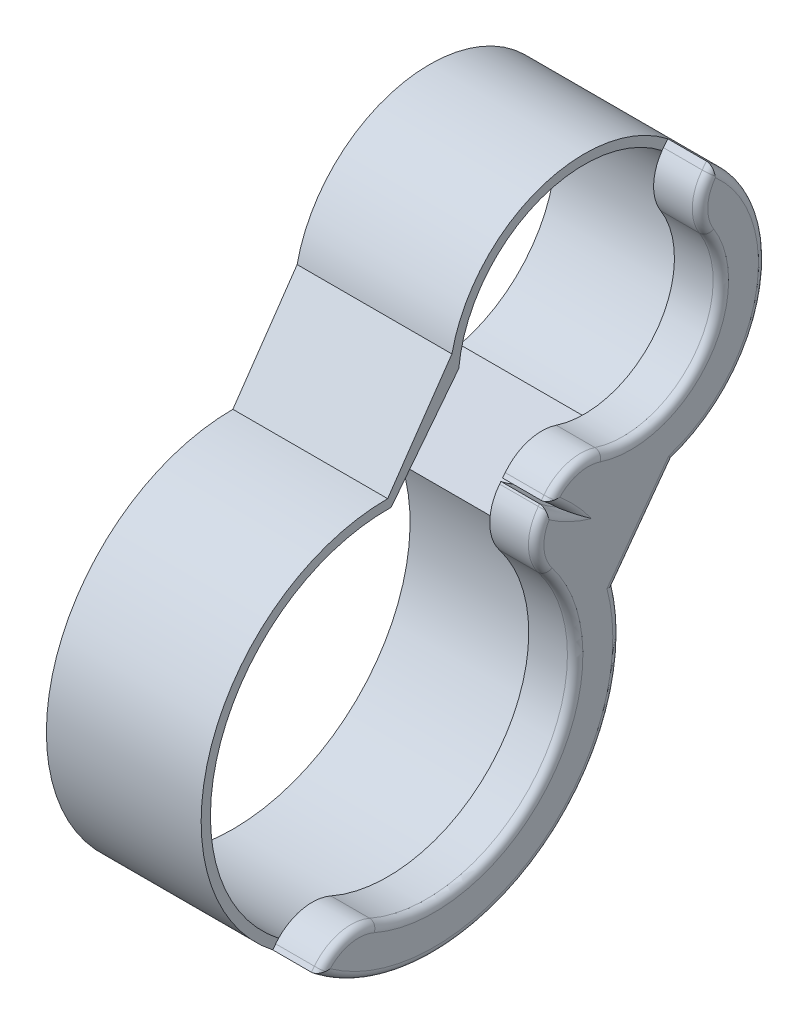
SolidWorks part; units mm, degrees
ref_plane "Front Plane" through (0, 0, 0) normal (0, 0, 1) x (1, 0, 0)
ref_plane "Top Plane" through (0, 0, 0) normal (0, 1, 0) x (1, 0, 0)
ref_plane "Right Plane" through (0, 0, 0) normal (1, 0, 0) x (0, 0, -1)
sketch "Sketch1" plane through (0, 0, 0) normal (1, 0, 0) x (0, 0, -1)
  line L0 (-26.7095, -28.8833) -> (-22.337, -23.2947)
  line L1 (-16.0369, -36.8188) -> (-12.2646, -31.9973)
  line L2 (-11.4506, -32.385) -> (-15.2204, -37.5072)
  line L3 (-22.7828, -22.2598) -> (-26.9349, -28.2811)
  circle A0 centre (-26.9349, -40.3311) radius 3
  circle A1 centre (-14.2256, -24.0867) radius 3
  arc A2 (-12.2646, -31.9973) -> (-22.337, -23.2947) centre (-14.2256, -24.0867) cw construction
  arc A3 (-26.7095, -28.8833) -> (-16.0369, -36.8188) centre (-26.9349, -40.3311) cw
  circle A4 centre (-26.9349, -40.3311) radius 11.45
  circle A5 centre (-14.2256, -24.0867) radius 8.15
  circle A6 centre (-14.2256, -24.0867) radius 8.75
  circle A7 centre (-26.9349, -40.3311) radius 12.05
  point P18 (0, 0)
  point P19 (-22.7828, -22.2598)
  dimension "D1" = 17.5
  dimension "D2" = 24.1
extrude "Boss-Extrude2" add sketch "Sketch1" along normal blind 10 contours A7 L0 A6 L3 | A7 L1 A4 L0 | A7 L2 A6 L1 | A6 L0 A5 L1 region at (0, -48.586, 35.3539) region at (0, -25.5356, 24.61) region at (0, -23.2057, 22.6832) region at (0, -34.7941, 13.7965)
sketch "Sketch4" plane through (10, 0, 0) normal (1, 0, 0) x (0, 0, -1)
  line L0 (-14.2256, -24.0867) -> (-8.8339, -17.1953)
  line L1 (-8.8339, -17.1953) -> (-34.3601, -49.8216)
  line L2 (-15.2204, -37.5072) -> (-11.4506, -32.385)
  line L3 (-26.9349, -28.2811) -> (-22.7828, -22.2598)
  circle A0 centre (-14.2256, -24.0867) radius 8.75
  circle A1 centre (-26.9349, -40.3311) radius 12.05
  circle A2 centre (-14.2256, -24.0867) radius 5.8229
  circle A3 centre (-26.9349, -40.3311) radius 9.1173
  line M1 (-12.2646, -31.9973) -> (-16.0369, -36.8188)
  arc M2 (-16.0369, -36.8188) -> (-26.7095, -28.8833) centre (-26.9349, -40.3311) cw
  arc M4 (-22.337, -23.2947) -> (-12.2646, -31.9973) centre (-14.2256, -24.0867) cw
  arc M6 (-26.9349, -28.2811) -> (-15.2204, -37.5072) centre (-26.9349, -40.3311) ccw
  line M7 (-15.2204, -37.5072) -> (-11.4506, -32.385)
  arc M8 (-11.4506, -32.385) -> (-22.7828, -22.2598) centre (-14.2256, -24.0867) ccw
extrude "Boss-Extrude4" add sketch "Sketch4" along normal blind 3 contours A1 L1 M6 M1 M2 | A3 L1 A1 A0 M2 M1 | A1 A0 M1 | A1 A0 M7 M1 | A2 L1 A1 A0 M1 M4 | A0 L0 M1 M8 M4 region at (10, -18.7091, 9.761) region at (10, -17.5375, 8.8834) region at (10, -31.6001, 19.2318) region at (10, -33.7773, 15.4624) region at (10, -34.7941, 13.7965) region at (10, -36.9483, 15.6332)
fillet "Fillet1" radius 3 4 edges at (11.5, -19.5007, 10.6376) (11.5, -28.6728, 17.8137) (11.5, -33.1504, 21.3169) (11.5, -47.5118, 32.5529)
fillet "Fillet2" radius 0.5 11 edges at (13, -25.5722, 5.6026) (13, -34.9461, 13.3355) (13, -50.4648, 20.4149) (13, -48.5168, 32.5386) (13, -45.9491, 19.7542) (13, -32.9225, 20.3379) (13, -31.3684, 19.0774) (13, -31.2647, 18.9974) (13, -29.5997, 17.8477) (13, -27.6748, 9.6396) (13, -19.2446, 9.7461)
